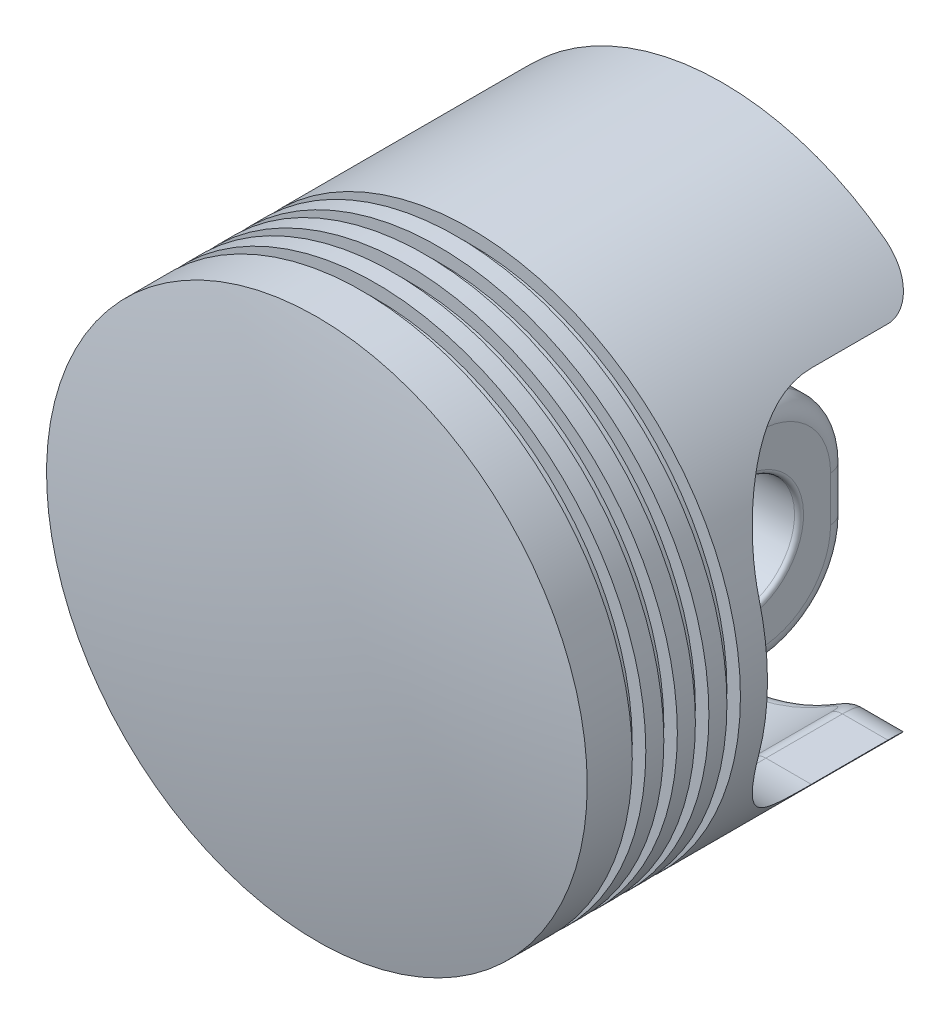
SolidWorks part; units mm, degrees
material "2618-T61 (SS)"
ref_plane "Front Plane" through (0, 0, 0) normal (1, 0, 0) x (0, 1, 0)
ref_plane "Top Plane" through (0, 0, 0) normal (0, 0, 1) x (0, 1, 0)
ref_plane "Right Plane" through (0, 0, 0) normal (0, 1, 0) x (-1, 0, 0)
sketch "Sketch1" plane through (0, 0, 0) normal (1, 0, 0) x (0, 1, 0)
  line L0 (0, 78.7988) -> (0, -66.0219) construction
  line L1 (-63.2814, 0) -> (100.6028, 0) construction
  line L2 (0, 40) -> (30, 40)
  line L3 (30, 62.5272) -> (30, 40)
  line L4 (26, 40) -> (26, 0)
  line L6 (28.5, 31.5) -> (30, 31.5)
  line L7 (28.5, 40) -> (28.5, 38.5)
  line L8 (28.5, 36.5) -> (30, 36.5)
  line L9 (30, 36.5) -> (30, 38.5)
  line L10 (30, 38.5) -> (28.5, 38.5)
  line L11 (28.5, 36.5) -> (28.5, 35)
  line L12 (28.5, 35) -> (30, 35)
  line L13 (30, 35) -> (30, 33)
  line L14 (30, 33) -> (28.5, 33)
  line L15 (28.5, 33) -> (28.5, 31.5)
  line L16 (30, 31.5) -> (30, 29.5)
  line L17 (30, 29.5) -> (28.5, 29.5)
  line L18 (28.5, 29.5) -> (28.5, 28)
  line L19 (28.5, 28) -> (30, 28)
  line L20 (30, 28) -> (30, 0)
  line L21 (26, 0) -> (30, 0)
  line L22 (0, 40) -> (0, 48)
  arc A0 (30, 45) -> (-30, 45) centre (0, -103.5) ccw
  point P12 (0, 48)
  dimension "D2" = 5
  dimension "D4" = 151.5
  dimension "D1" = 8
  dimension "D3" = 60
  dimension "D5" = 4
  dimension "D6" = 12
  dimension "D7" = 1.5
  dimension "D8" = 2
  dimension "D9" = 40
revolve "Revolve1" add sketch "Sketch1" angle 360 about L0 region at (0, 13.9313, 43.5589) region at (0, 27.9255, 19.1656)
sketch "Sketch2" plane through (0, 0, 0) normal (1, 0, 0) x (0, 1, 0)
  line L0 (-30, 0) -> (30, 0) construction
  line L1 (-7.5, 25) -> (7.5, 25)
  line L2 (-20, 12.5) -> (-20, 0)
  line L3 (-20, 0) -> (20, 0)
  line L4 (20, 12.5) -> (20, 0)
  line L5 (-20, 25) -> (20, 0) construction
  line L6 (-20, 0) -> (20, 25) construction
  arc A0 (7.5, 25) -> (20, 12.5) centre (7.5, 12.5) cw
  arc A1 (-7.5, 25) -> (-20, 12.5) centre (-7.5, 12.5) ccw
  point P0 (0, 12.5)
  dimension "D3" = 12.5
  dimension "D1" = 40
  dimension "D2" = 25
extrude "Cut-Extrude1" cut sketch "Sketch2" against normal through all both and the other way through all
fillet "Fillet1" radius 4 4 edges at (19.487, 20, 0) (-19.487, 20, 0) (-19.487, -20, 0) (19.487, -20, 0)
sketch "Sketch3" plane through (0, 0, 40) normal (0, 0, -1) x (1, 0, 0)
  line L0 (0, 16.8707) -> (0, -26.7203) construction
  line L1 (-19.217, 0) -> (29.506, 0) construction
  line L2 (16, -12.5) -> (10, -12.5)
  line L3 (-16, 12.5) -> (-10, 12.5)
  line L4 (-16, 12.5) -> (-16, -12.5)
  line L5 (-16, -12.5) -> (-10, -12.5)
  line L6 (-10, 12.5) -> (-10, -12.5)
  line L7 (10, 12.5) -> (10, -12.5)
  line L8 (16, 12.5) -> (10, 12.5)
  line L9 (16, 12.5) -> (16, -12.5)
  point P9 (-16, 0)
  dimension "D1" = 6
  dimension "D2" = 25
  dimension "D3" = 20
extrude "Boss-Extrude1" add sketch "Sketch3" along normal blind 38
fillet "Fillet2" radius 10 4 edges at (13, 12.5, 2) (13, -12.5, 2) (-13, -12.5, 2) (-13, 12.5, 2)
sketch "Sketch4" plane through (-16, 0, 0) normal (-1, 0, 0) x (0, -1, 0)
  line L2 (-30, 0) -> (-24, 0) construction
  circle A0 centre (0, 14) radius 6.5
  dimension "D1" = 13
  dimension "D2" = 14
extrude "Cut-Extrude2" cut sketch "Sketch4" against normal through all both and the other way through all
fillet "Fillet3" radius 0.5 4 edges at (16, -6.5, 14) (10, 0, 7.5) (-10, 0, 20.5) (-16, 0, 7.5)
fillet "Fillet5" radius 2 20 edges at (10, 12.5, 26) (10, -12.5, 26) (10, -9.5711, 4.9289) (10, 0, 2) (16, -12.5, 26) (16, -9.5711, 4.9289) (16, 0, 2) (16, 12.5, 26) (-16, 12.5, 26) (-16, -12.5, 26) (-16, -9.5711, 4.9289) (-16, 0, 2) (-10, -12.5, 26) (-10, -9.5711, 4.9289) (-10, 0, 2) (-10, 12.5, 26) (10, 9.5711, 4.9289) (16, 9.5711, 4.9289) (-16, 9.5711, 4.9289) (-10, 9.5711, 4.9289)
fillet "Fillet4" radius 2 16 edges at (13, 12.5, 40) (16, 0, 40) (13, -12.5, 40) (10, 0, 40) (-13, -12.5, 40) (-10, 0, 40) (-13, 12.5, 40) (-16, 0, 40) (10.5858, -11.9142, 40) (15.4142, -11.9142, 40) (15.4142, 11.9142, 40) (10.5858, 11.9142, 40) (-15.4142, -11.9142, 40) (-10.5858, -11.9142, 40) (-10.5858, 11.9142, 40) (-15.4142, 11.9142, 40)
fillet "Fillet6" radius 2 16 edges at (-16.6132, -20, 8.25) (-15.8382, -20.6192, 1.8622) (0, -26, 0) (16.0798, -20.4313, 2.1931) (16.6132, -20, 8.25) (18.595, -18.1722, 19.0081) (26, 0, 25) (18.3671, 18.4025, 18.6144) (16.6132, 20, 8.25) (15.8382, 20.6192, 1.8622) (0, 26, 0) (-16.0798, 20.4313, 2.1931) (-16.6132, 20, 8.25) (-18.595, 18.1722, 19.0081) (-26, 0, 25) (-18.3671, -18.4025, 18.6144)
